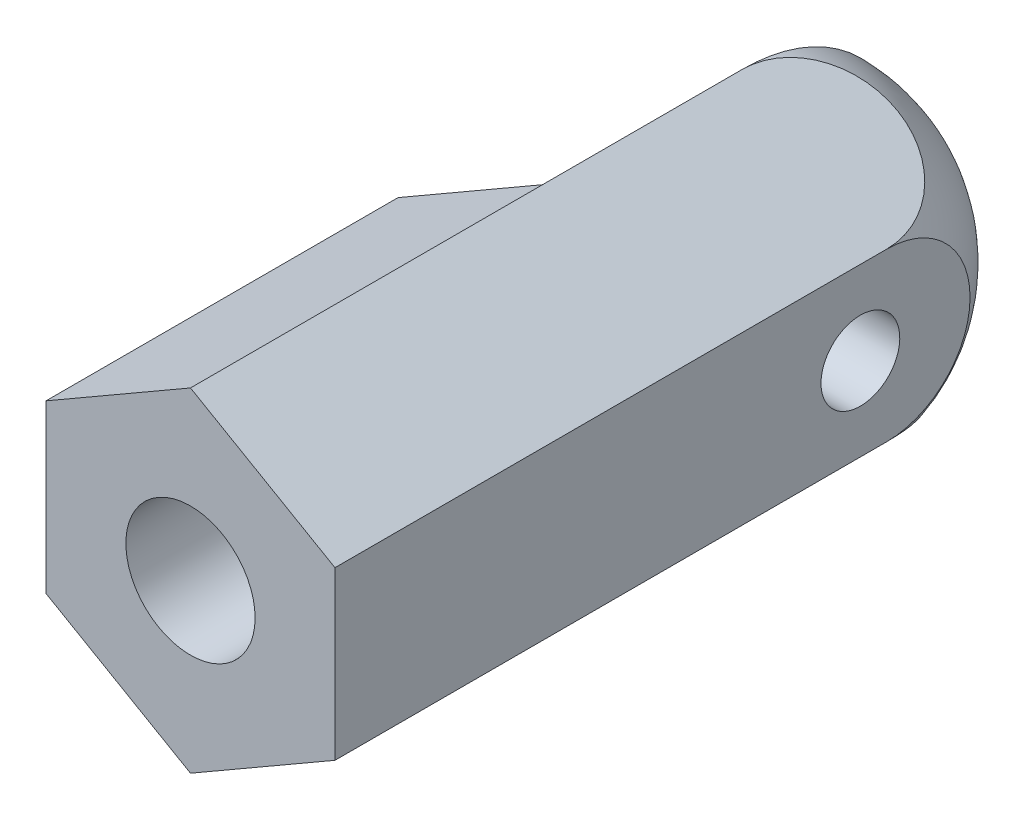
SolidWorks part; units mm, degrees
material "1.0503 (C45)"
ref_plane "Ebene vorne" through (0, 0, 0) normal (0, 0, 1) x (1, 0, 0)
ref_plane "Ebene oben" through (0, 0, 0) normal (0, 1, 0) x (1, 0, 0)
ref_plane "Ebene rechts" through (0, 0, 0) normal (1, 0, 0) x (0, 0, -1)
sketch "Skizze1" plane through (0, 0, 0) normal (0, 0, 1) x (1, 0, 0)
  line L1 (-2.75, 1.5877) -> (-2.75, -1.5877)
  line L2 (-2.75, -1.5877) -> (0, -3.1754)
  line L3 (0, -3.1754) -> (2.75, -1.5877)
  line L4 (2.75, -1.5877) -> (2.75, 1.5877)
  line L5 (2.75, 1.5877) -> (0, 3.1754)
  line L6 (0, 3.1754) -> (-2.75, 1.5877)
  circle A0 centre (0, 0) radius 2.75 construction
  circle A1 centre (0, 0) radius 1.23
  dimension "D2" = 2.46
  dimension "D1" = 5.5
extrude "Aufsatz-Linear austragen1" add sketch "Skizze1" against normal blind 15 contours L6 L1 L2 L3 L4 L5
extrude "Schnitt-Linear austragen3" cut sketch "Skizze1<3>" against normal blind 6 flip side to cut
sketch "Skizze1<3>" plane through (0, 0, 0) normal (0, 0, 1) x (1, 0, 0) same geometry as "Skizze1"
sketch "Skizze2" plane through (0, 0, 0) normal (1, 0, 0) x (0, 0, -1)
  line L2 (0, 0) -> (13.6754, 0) construction
  line L3 (10.5, 3.1754) -> (10.5, 5)
  line L4 (10.5, 5) -> (15, 5)
  line L5 (15, 5) -> (15, 0)
  line L6 (15, 0) -> (13.6754, 0)
  line L7 (15, 3.1754) -> (0, 3.1754) construction
  line L9 (15, -1.5877) -> (15, 1.5877) construction
  arc A0 (10.5, 3.1754) -> (13.6754, 0) centre (10.5, 0) cw
  dimension "D1" = 10.5
  dimension "D2" = 5
revolve "Schnitt-Rotation1" cut sketch "Skizze2" angle 360 about L2
sketch "Skizze3" plane through (2.75, 0, 0) normal (1, 0, 0) x (0, 0, -1)
  line L0 (0, 0) -> (10, 0) construction
  circle A0 centre (10, 0) radius 0.75
  dimension "D2" = 1.5
  dimension "D1" = 10
extrude "Schnitt-Linear austragen1" cut sketch "Skizze3" against normal through all
sketch "Skizze4" plane through (0, 0, 0) normal (0, 1, 0) x (1, 0, 0)
  line L0 (-2.75, 10.5) -> (-2.75, 0) construction
  line L1 (-2.75, 6.7) -> (0, 6.7)
  line L2 (-2.75, 6.7) -> (-2.75, 13.6754)
  line L3 (-2.75, 13.6754) -> (0, 13.6754)
  line L4 (0, 6.7) -> (0, 13.6754)
  line L7 (2.75, 9.25) -> (2.75, 10.75) construction
  arc A0 (2.75, 12.0877) -> (-2.75, 12.0877) centre (0, 10.5) ccw construction
  point P11 (2.75, 10)
  dimension "D1" = 3.3
extrude "Schnitt-Linear austragen2" cut sketch "Skizze4" against normal through all and the other way through all
ref_axis "Schraubachse" through (0, 0, -6) along (0, 0, 1)
ref_axis "Knickachse" through (0, 0, -10) along (1, 0, 0)
